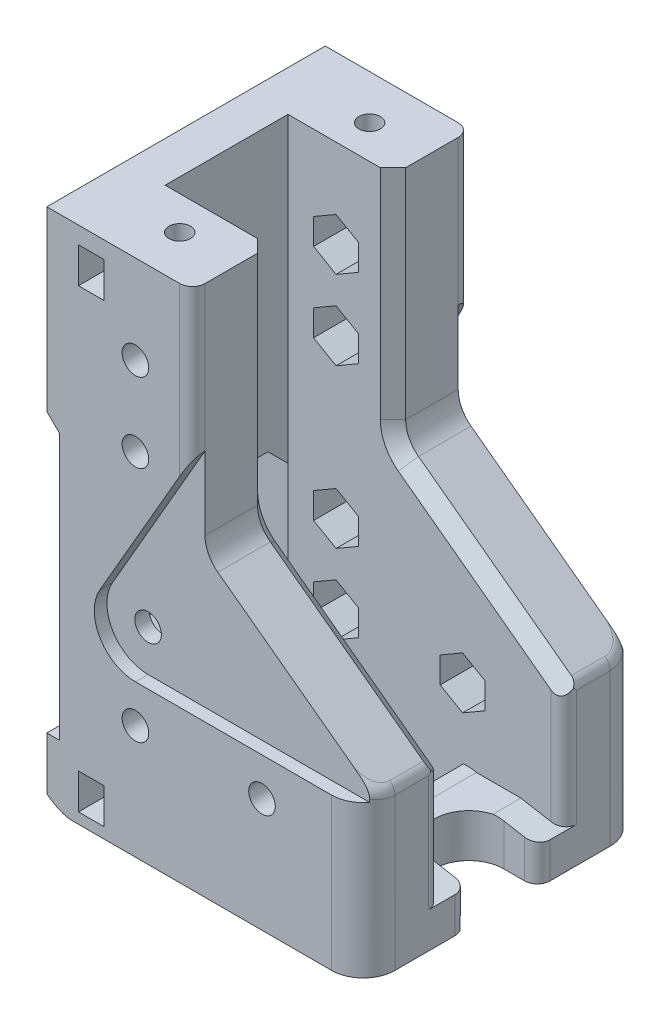
SolidWorks part; units mm, degrees
material "3D printed plastic"
ref_plane "Front Plane" through (0, 0, 0) normal (0, 0, 1) x (1, 0, 0)
ref_plane "Top Plane" through (0, 0, 0) normal (0, 1, 0) x (1, 0, 0)
ref_plane "Right Plane" through (0, 0, 0) normal (1, 0, 0) x (0, 0, -1)
sketch "Sketch1" plane through (0, 0, 0) normal (0, 0, 1) x (1, 0, 0)
  line L0 (0, 0) -> (0, 82)
  line L1 (0, 82) -> (23, 82)
  line L2 (23, 82) -> (23, 47.5186)
  line L3 (25.0239, 43.5008) -> (50, 25)
  line L7 (50, 0) -> (0, 0)
  line L8 (23, 47.5186) -> (23, 45) construction
  line L9 (23, 45) -> (25.0239, 43.5008) construction
  line L12 (50, 25) -> (50, 0)
  arc A1 (23, 47.5186) -> (25.0239, 43.5008) centre (28, 47.5186) ccw
  dimension "D3" = 50
  dimension "D6" = 5
  dimension "D1" = 23
  dimension "D2" = 82
  dimension "D4" = 45
  dimension "D5" = 25
extrude "Boss-Extrude1" add sketch "Sketch1" along normal mid plane 44
sketch "Sketch3" plane through (0, 0, 0) normal (0, 0, 1) x (1, 0, 0)
  line L0 (6.4, 0) -> (6.4, 82)
  line L1 (0, 0) -> (50, 0) construction
  line L2 (23, 82) -> (0, 82) construction
  line L3 (6.4, 0) -> (33.2, 0)
  line L4 (33.2, 0) -> (33.2, 6.8374)
  line L5 (34.7, 7) -> (34.7, 0) construction
  line L6 (0, 82) -> (0, 0) construction
  line L7 (36.2, 6.8374) -> (43.2, 6.8374)
  line L8 (43.2, 6.8374) -> (50, 5.6384)
  line L9 (50, 0) -> (50, 25) construction
  line L11 (50, 25) -> (23, 82)
  line L12 (23, 47.5186) -> (23, 82) construction
  line L13 (23, 82) -> (6.4, 82)
  line L14 (50, 5.6384) -> (50, 25)
  line L15 (50, 25) -> (25.0239, 43.5008) construction
  arc A0 (33.2, 6.8374) -> (36.2, 6.8374) centre (34.7, 0) cw
  dimension "D3" = 6.4
  dimension "D1" = 26.8
  dimension "D2" = 7
  dimension "D4" = 1.5
  dimension "D6" = 10
  dimension "D8" = 10
extrude "Cut-Extrude1" cut sketch "Sketch3" against normal blind 9.7 and the other way blind 9.7
chamfer "Chamfer1" distance 1 angle 80 1 edges at (6.4, 0, 0) first distance on face at (25, 0, 0)
sketch "Sketch7" plane through (0, 0, 0) normal (-1, 0, 0) x (0, 0, 1)
  line L0 (-10.35, 38.5) -> (-0.55, 48.3)
  line L1 (-10.35, 38.5) -> (9.25, 38.5) construction
  line L2 (-11.15, 32.8) -> (-11.15, 5.5)
  line L3 (-11.15, 5.5) -> (10.05, 5.5)
  line L4 (10.05, 32.8) -> (10.05, 5.5)
  line L5 (-0.55, 48.3) -> (9.25, 38.5)
  line L6 (-0.55, 5.5) -> (-0.55, 17.3042) construction
  line L8 (22, 0) -> (-22, 0) construction
  line L9 (-11.15, 32.8) -> (-10.35, 33.6)
  line L10 (-10.35, 33.6) -> (-10.35, 38.5)
  line L11 (10.05, 32.8) -> (9.25, 33.6)
  line L12 (9.25, 33.6) -> (9.25, 38.5)
  dimension "D1" = 21.2
  dimension "D2" = 0.55
  dimension "D3" = 5.5
  dimension "D4" = 0.8
  dimension "D5" = 33
  dimension "D6" = 27.3
extrude "Cut-Extrude5" cut sketch "Sketch7" against normal blind 6.4
sketch "Sketch9" plane through (0, 0, -11.15) normal (0, 0, 1) x (1, 0, 0)
  line L0 (6.4, 8) -> (2.2, 8)
  line L1 (6.4, 32.8) -> (6.4, 5.5) construction
  line L2 (2.2, 8) -> (2.2, 5.5)
  line L3 (6.4, 5.5) -> (0, 5.5) construction
  line L4 (2.2, 5.5) -> (6.3698, 5.5)
  line L6 (6.3698, 5.5) -> (6.4, 5.6713)
  line L7 (6.4, 5.6713) -> (6.4, 8)
  line L8 (6.3698, 5.5) -> (5.4, 0) construction
  dimension "D1" = 4.2
  dimension "D2" = 2.5
extrude "Boss-Extrude3" add sketch "Sketch9" along normal up to next
sketch "Sketch10" plane through (0, 0, -11.15) normal (0, 0, 1) x (1, 0, 0)
  line L3 (6.4, 5.6713) -> (6.3698, 5.5)
  line L4 (6.3698, 5.5) -> (6.4, 5.5)
  line L5 (6.4, 5.5) -> (6.4, 5.6713)
  line L6 (6.4, 5.6713) -> (6.3698, 5.5)
  line L7 (6.3698, 5.5) -> (6.4, 5.5)
  line L8 (6.4, 5.5) -> (6.4, 5.6713)
  dimension "D1" = 0
extrude "Boss-Extrude4" add sketch "Sketch10" along normal up to surface (1.45 mm away) up to face at (22.5073, 23.1196, -9.7)
sketch "Sketch12" plane through (2.2, 0, 0) normal (-1, 0, 0) x (0, 0, 1)
  line L0 (-11.15, 32.8) -> (-11.15, 5.5) construction
  line L1 (-11.15, 10) -> (-10.25, 10)
  line L2 (-11.15, 10) -> (-11.15, 5.5)
  line L3 (-11.15, 5.5) -> (-10.25, 5.5)
  line L4 (-10.25, 10) -> (-10.25, 5.5)
  line L5 (-11.15, 5.5) -> (10.05, 5.5) construction
  line L6 (7.15, 5.5) -> (9.7481, 10)
  line L7 (9.7481, 10) -> (10.05, 10)
  line L9 (10.05, 10) -> (10.05, 5.5)
  line L10 (10.05, 5.5) -> (7.15, 5.5)
  line L11 (10.05, 5.5) -> (10.05, 32.8) construction
  dimension "D1" = 0.9
  dimension "D2" = 2.9
  dimension "D3" = 4.5
  dimension "D4" = 60
extrude "Boss-Extrude5" add sketch "Sketch12" along normal up to surface (2.2 mm away) up to face at (0, 29.9, -0.55)
sketch "Sketch13" plane through (0, 0, 0) normal (-1, 0, 0) x (0, 0, 1)
  line L0 (-16, 76.5) -> (16, 76.5) construction
  line L1 (16, 76.5) -> (16, 4.5) construction
  line L2 (16, 4.5) -> (-16, 4.5) construction
  line L3 (-16, 4.5) -> (-16, 76.5) construction
  line L4 (0, 4.5) -> (0, 0) construction
  line L5 (22, 0) -> (-22, 0) construction
  circle A0 centre (-16, 4.5) radius 1.75
  circle A1 centre (16, 4.5) radius 1.75
  circle A2 centre (16, 76.5) radius 1.75
  circle A3 centre (-16, 76.5) radius 1.75
  dimension "D2" = 3.5
  dimension "D1" = 32
  dimension "D3" = 72
  dimension "D4" = 4.5
extrude "Cut-Extrude6" cut sketch "Sketch13" against normal blind 13
sketch "Sketch14" plane through (6.4, 0, 0) normal (1, 0, 0) x (0, 0, -1)
  line L0 (-9.25, 33.6) -> (-5.45, 37.4)
  line L1 (-5.45, 37.4) -> (-5.45, 42.3) construction
  line L3 (-9.25, 38.5) -> (0.55, 48.3) construction
  line L4 (-5.45, 42.3) -> (-9.25, 38.5)
  line L5 (-9.25, 38.5) -> (-9.25, 33.6)
  line L6 (-9.7, 33.15) -> (-9.25, 33.6) construction
  line L7 (10.35, 33.6) -> (6.55, 37.4)
  line L8 (6.55, 37.4) -> (6.55, 42.3) construction
  line L9 (0.55, 48.3) -> (10.35, 38.5) construction
  line L10 (6.55, 42.3) -> (10.35, 38.5)
  line L11 (10.35, 38.5) -> (10.35, 33.6)
  line L12 (10.35, 33.6) -> (11.15, 32.8) construction
  line L13 (6.55, 37.4) -> (-5.45, 37.4)
  line L14 (-5.45, 42.3) -> (0.55, 48.3)
  line L15 (0.55, 48.3) -> (6.55, 42.3)
  dimension "D1" = 12
extrude "Boss-Extrude6" add sketch "Sketch14" against normal offset from surface (4.2 mm away) 2.2 up to face at (0, 76.5, -14.25)
sketch "Sketch15" plane through (0, 0, 9.25) normal (0, 0, -1) x (-1, 0, 0)
  line L0 (-2.2, 39.9) -> (0, 42.1)
  line L1 (0, 42.1) -> (0, 48.3)
  line L2 (0, 48.3) -> (-2.2, 48.3)
  line L3 (-2.2, 48.3) -> (-2.2, 39.9)
  line L4 (-2.2, 38.5) -> (-2.2, 48.3) construction
  line L5 (0, 38.5) -> (0, 48.3) construction
  line L6 (-2.2, 37.4) -> (-6.4, 37.4) construction
  dimension "D1" = 45
  dimension "D2" = 2.5
extrude "Boss-Extrude7" add sketch "Sketch15" along normal up to surface (19.6 mm away) up to face at (1.1, 36.05, -10.35)
sketch "Sketch20" plane through (0, 0, 0) normal (-1, 0, 0) x (0, 0, 1)
  line L0 (-14.3834, 79.3) -> (-13.3834, 79.3)
  line L1 (-19.2332, 76.5) -> (-17.6166, 73.7) construction
  line L2 (-17.6166, 73.7) -> (-14.3834, 73.7)
  line L3 (-14.3834, 73.7) -> (-12.7668, 76.5) construction
  line L4 (-12.7668, 76.5) -> (-14.3834, 79.3) construction
  line L5 (-14.3834, 79.3) -> (-17.6166, 79.3)
  line L6 (-17.6166, 79.3) -> (-19.2332, 76.5) construction
  line L7 (-13.3834, 79.3) -> (-11.7668, 76.5)
  line L8 (-11.7668, 76.5) -> (-13.3834, 73.7)
  line L9 (-13.3834, 73.7) -> (-14.3834, 73.7)
  line L10 (-17.6166, 79.3) -> (-22, 79.3)
  line L11 (-22, 82) -> (-22, 0) construction
  line L12 (-22, 79.3) -> (-22, 73.7)
  line L13 (-22, 73.7) -> (-17.6166, 73.7)
  line L15 (-22, 40.5) -> (-9.5422, 40.5) construction
  line L16 (-17.6166, 1.7) -> (-19.2332, 4.5) construction
  line L17 (-12.7668, 4.5) -> (-14.3834, 1.7) construction
  line L18 (-14.3834, 7.3) -> (-12.7668, 4.5) construction
  line L19 (-19.2332, 4.5) -> (-17.6166, 7.3) construction
  line L20 (-22, 7.3) -> (-17.6166, 7.3)
  line L21 (-22, 1.7) -> (-22, 7.3)
  line L22 (-17.6166, 1.7) -> (-22, 1.7)
  line L23 (-13.3834, 7.3) -> (-14.3834, 7.3)
  line L24 (-11.7668, 4.5) -> (-13.3834, 7.3)
  line L25 (-13.3834, 1.7) -> (-11.7668, 4.5)
  line L26 (-14.3834, 1.7) -> (-17.6166, 1.7)
  line L27 (-17.6166, 7.3) -> (-14.3834, 7.3)
  line L28 (-14.3834, 1.7) -> (-13.3834, 1.7)
  line L29 (0, 0) -> (0, 46.601) construction
  line L30 (19.2332, 4.5) -> (17.6166, 7.3) construction
  line L31 (14.3834, 7.3) -> (12.7668, 4.5) construction
  line L32 (12.7668, 4.5) -> (14.3834, 1.7) construction
  line L33 (17.6166, 1.7) -> (19.2332, 4.5) construction
  line L34 (22, 40.5) -> (9.5422, 40.5) construction
  line L35 (17.6166, 79.3) -> (19.2332, 76.5) construction
  line L36 (12.7668, 76.5) -> (14.3834, 79.3) construction
  line L37 (14.3834, 73.7) -> (12.7668, 76.5) construction
  line L38 (19.2332, 76.5) -> (17.6166, 73.7) construction
  line L39 (14.3834, 1.7) -> (13.3834, 1.7)
  line L40 (17.6166, 7.3) -> (14.3834, 7.3)
  line L41 (14.3834, 1.7) -> (17.6166, 1.7)
  line L42 (13.3834, 1.7) -> (11.7668, 4.5)
  line L43 (11.7668, 4.5) -> (13.3834, 7.3)
  line L44 (13.3834, 7.3) -> (14.3834, 7.3)
  line L45 (17.6166, 1.7) -> (22, 1.7)
  line L46 (22, 1.7) -> (22, 7.3)
  line L47 (22, 7.3) -> (17.6166, 7.3)
  line L48 (22, 73.7) -> (17.6166, 73.7)
  line L49 (22, 79.3) -> (22, 73.7)
  line L50 (17.6166, 79.3) -> (22, 79.3)
  line L51 (13.3834, 73.7) -> (14.3834, 73.7)
  line L52 (11.7668, 76.5) -> (13.3834, 73.7)
  line L53 (13.3834, 79.3) -> (11.7668, 76.5)
  line L54 (14.3834, 79.3) -> (17.6166, 79.3)
  line L55 (17.6166, 73.7) -> (14.3834, 73.7)
  line L56 (14.3834, 79.3) -> (13.3834, 79.3)
  circle A0 centre (-16, 76.5) radius 2.8 construction
  circle A1 centre (-16, 4.5) radius 2.8 construction
  circle A2 centre (16, 4.5) radius 2.8 construction
  circle A3 centre (16, 76.5) radius 2.8 construction
  dimension "D1" = 5.6
  dimension "D2" = 1
extrude "Cut-Extrude10" cut sketch "Sketch20" against normal blind 4 from offset 5 offset against normal yes
fillet "Fillet1" radius 5 2 edges at (50, 12.5, -22) (50, 12.5, 22)
sketch "Sketch22" plane through (0, 0, 0) normal (0, -1, 0) x (1, 0, 0)
  line L0 (0, 22) -> (0, 18)
  line L1 (0, 22) -> (0, -22) construction
  line L2 (0, 22) -> (4, 22)
  line L3 (0, 22) -> (45, 22) construction
  line L4 (0, 0) -> (14.495, 0) construction
  line L5 (0, -22) -> (4, -22)
  line L6 (0, -22) -> (0, -18)
  arc A0 (4, 22) -> (0, 18) centre (4, 18) ccw
  arc A2 (4, -22) -> (0, -18) centre (4, -18) cw
  dimension "D1" = 4
extrude "Cut-Extrude12" cut sketch "Sketch22" against normal blind 2
chamfer "Chamfer5" distance 2 angle 45 2 edges at (1.1716, 2, -20.8284) (1.1716, 2, 20.8284)
chamfer "Chamfer6" distance 1 angle 45 1 edges at (33.2, 6.8374, 0) first distance on face at (34.7, 6.9187, 0)
chamfer "Chamfer8" distance 2 angle 45 6 edges at (37.5119, 34.2504, 9.7) (23.5345, 45.2693, 9.7) (23, 64.7593, 9.7) (37.5119, 34.2504, -9.7) (23.5345, 45.2693, -9.7) (23, 64.7593, -9.7)
fillet "Fillet2" radius 2 12 edges at (23, 64.7593, 22) (23.5345, 45.2693, 22) (35.0119, 36.1023, 22) (23, 64.7593, -22) (23.5345, 45.2693, -22) (35.0119, 36.1023, -22) (48.5355, 26.0848, -20.5355) (48.5355, 26.0848, 20.5355) (50, 14.0747, 9.7) (50, 14.0747, -9.7) (50, 25, -14.35) (50, 25, 14.35)
sketch "Sketch34" plane through (0, 0, -22) normal (0, 0, -1) x (-1, 0, 0)
  line L0 (-34, 18) -> (-14, 18) construction
  line L1 (-14, 18) -> (-14, 43) construction
  line L2 (-14, 43) -> (-14, 68) construction
  line L3 (0, 82) -> (0, 1.6569) construction
  line L4 (-4, 0) -> (-45, 0) construction
  circle A0 centre (-14, 68) radius 2.1
  circle A1 centre (-14, 43) radius 2.1 construction
  circle A2 centre (-14, 18) radius 2.1
  circle A3 centre (-34, 18) radius 2.1
  circle A4 centre (-14, 30.5) radius 2.1
  circle A5 centre (-14, 55.5) radius 2.1
  dimension "D1" = 4.2
  dimension "D2" = 25
  dimension "D3" = 14
  dimension "D4" = 18
  dimension "D5" = 20
extrude "Cut-Extrude21" cut sketch "Sketch34" against normal blind 16
sketch "Sketch35" plane through (0, 0, -9.7) normal (0, 0, 1) x (1, 0, 0)
  line L1 (14, 72.0992) -> (10.45, 70.0496)
  line L2 (10.45, 70.0496) -> (10.45, 65.9504)
  line L3 (10.45, 65.9504) -> (14, 63.9008)
  line L4 (14, 63.9008) -> (17.55, 65.9504)
  line L5 (17.55, 65.9504) -> (17.55, 70.0496)
  line L6 (17.55, 70.0496) -> (14, 72.0992)
  line L7 (14, 51.4008) -> (17.55, 53.4504)
  line L8 (17.55, 53.4504) -> (17.55, 57.5496)
  line L9 (17.55, 57.5496) -> (14, 59.5992)
  line L10 (14, 59.5992) -> (10.45, 57.5496)
  line L11 (10.45, 57.5496) -> (10.45, 53.4504)
  line L12 (10.45, 53.4504) -> (14, 51.4008)
  line L13 (14, 22.0992) -> (10.45, 20.0496)
  line L14 (10.45, 20.0496) -> (10.45, 15.9504)
  line L15 (10.45, 15.9504) -> (14, 13.9008)
  line L16 (14, 13.9008) -> (17.55, 15.9504)
  line L17 (17.55, 15.9504) -> (17.55, 20.0496)
  line L18 (17.55, 20.0496) -> (14, 22.0992)
  line L19 (34, 22.0992) -> (30.45, 20.0496)
  line L20 (30.45, 20.0496) -> (30.45, 15.9504)
  line L21 (30.45, 15.9504) -> (34, 13.9008)
  line L22 (34, 13.9008) -> (37.55, 15.9504)
  line L23 (37.55, 15.9504) -> (37.55, 20.0496)
  line L24 (37.55, 20.0496) -> (34, 22.0992)
  line L25 (14, 26.4008) -> (17.55, 28.4504)
  line L26 (17.55, 28.4504) -> (17.55, 32.5496)
  line L27 (17.55, 32.5496) -> (14, 34.5992)
  line L28 (14, 34.5992) -> (10.45, 32.5496)
  line L29 (10.45, 32.5496) -> (10.45, 28.4504)
  line L30 (10.45, 28.4504) -> (14, 26.4008)
  circle A0 centre (14, 68) radius 3.55 construction
  circle A1 centre (14, 55.5) radius 3.55 construction
  circle A2 centre (14, 18) radius 3.55 construction
  circle A3 centre (34, 18) radius 3.55 construction
  circle A4 centre (14, 30.5) radius 3.55 construction
  dimension "D1" = 7.1
extrude "Cut-Extrude22" cut sketch "Sketch35" against normal blind 8
mirror "Mirror1" about plane through (0, 0, 0) normal (0, 0, 1) of "Cut-Extrude22", "Cut-Extrude21"
sketch "Sketch38" plane through (0, 0, -22) normal (0, 0, -1) x (-1, 0, 0)
  line L0 (-8.3708, 33.75) -> (-39.1147, 87)
  line L1 (-39.1147, 87) -> (-75.4878, 24)
  line L2 (-75.4878, 24) -> (-14, 24)
  line L3 (-14, 30.5) -> (-57.3013, 55.5) construction
  line L4 (0, 82) -> (0, 1.6569) construction
  arc A0 (-14, 24) -> (-8.3708, 33.75) centre (-14, 30.5) ccw
  dimension "D1" = 6.5
  dimension "D2" = 60
  dimension "D3" = 30
  dimension "D4" = 50
extrude "Cut-Extrude25" cut sketch "Sketch38" against normal blind 2
mirror "Mirror2" about plane through (0, 0, 0) normal (0, 0, 1) of "Cut-Extrude25"
sketch "Sketch39" plane through (0, 82, 0) normal (0, 1, 0) x (1, 0, 0)
  line L0 (14, 0) -> (0, 0) construction
  line L2 (14, -15) -> (14, 0) construction
  line L3 (14, 0) -> (14, 15) construction
  circle A2 centre (14, -15) radius 1.7
  circle A3 centre (14, 15) radius 1.7
  dimension "D1" = 3.4
  dimension "D2" = 14
  dimension "D5" = 30
extrude "Cut-Extrude26" cut sketch "Sketch39" against normal blind 14
sketch "Sketch40" plane through (0, 0, 0) normal (-1, 0, 0) x (0, 0, 1)
  line L0 (22, 82) -> (22, 1.6569) construction
  line L1 (22, 52) -> (16.5, 52)
  line L2 (22, 52) -> (22, 10)
  line L3 (22, 10) -> (16.5, 10)
  line L4 (16.5, 52) -> (16.5, 10)
  line L5 (-22, 82) -> (-22, 1.6569) construction
  line L6 (-22, 10) -> (-16.5, 10)
  line L7 (-22, 10) -> (-22, 52)
  line L8 (-22, 52) -> (-16.5, 52)
  line L9 (-16.5, 10) -> (-16.5, 52)
  line L10 (-16, 76.5) -> (16, 76.5) construction
  line L11 (-11.75, 69) -> (-5.75, 69)
  line L12 (-11.75, 69) -> (-11.75, 43)
  line L13 (-11.75, 43) -> (-5.75, 43)
  line L14 (-5.75, 69) -> (-5.75, 43)
  line L15 (5.75, 69) -> (11.75, 69)
  line L16 (5.75, 69) -> (5.75, 43)
  line L17 (5.75, 43) -> (11.75, 43)
  line L18 (11.75, 69) -> (11.75, 43)
  line L19 (-5.75, 69) -> (-11.75, 43) construction
  line L20 (11.75, 43) -> (5.75, 69) construction
  line L21 (-8.75, 56) -> (8.75, 56) construction
  line L22 (0, 56) -> (0, 76.5) construction
  circle A0 centre (-16, 4.5) radius 1.75 construction
  circle A1 centre (-16, 4.5) radius 1.75 construction
  dimension "D1" = 5.5
  dimension "D2" = 42
  dimension "D3" = 5.5
  dimension "D4" = 6
  dimension "D5" = 26
  dimension "D6" = 51.5
  dimension "D7" = 17.5
extrude "Cut-Extrude27" cut sketch "Sketch40" against normal blind 2
chamfer "Chamfer9" distance 2 angle 45 4 edges at (0, 52, 19.25) (0, 69, 8.75) (0, 69, -8.75) (0, 52, -19.25)
sketch "Sketch41" plane through (0, 6.8374, 0) normal (0, 1, 0) x (1, 0, 0)
  line L0 (44.7, 0) -> (50, 0) construction
  line L1 (50, -11.7) -> (50, 11.7) construction
  line L2 (44.7, 5.5) -> (50, 5.5)
  line L3 (44.7, -5.5) -> (50, -5.5)
  line L4 (33.2, -9.7) -> (33.2, 9.7) construction
  arc A0 (44.7, 5.5) -> (44.7, -5.5) centre (44.7, 0) ccw
  arc A1 (50, -5.5) -> (50, 5.5) centre (50, 0) ccw
  point P4 (47.35, 0)
  dimension "D1" = 11.5
  dimension "D2" = 11
extrude "Cut-Extrude28" cut sketch "Sketch41" against normal through all
fillet "Fillet3" radius 2 2 edges at (50, 2.8192, 5.5) (50, 2.8192, -5.5)
